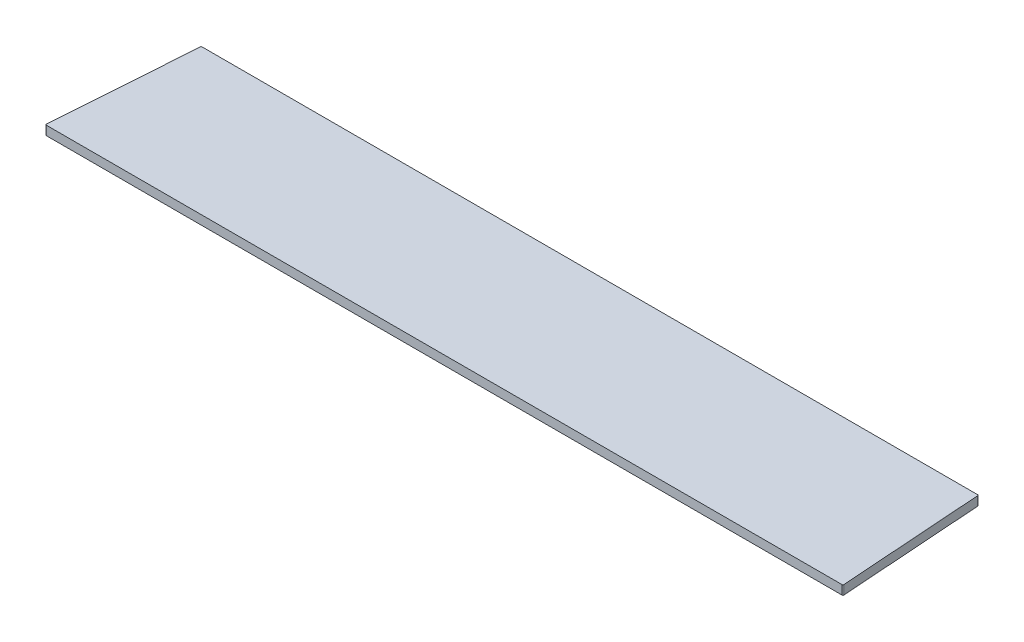
SolidWorks part; units mm, degrees
material "MS-Grade 400"
ref_plane "Front Plane" through (0, 0, 0) normal (0, 0, 1) x (1, 0, 0)
ref_plane "Top Plane" through (0, 0, 0) normal (0, 1, 0) x (1, 0, 0)
ref_plane "Right Plane" through (0, 0, 0) normal (1, 0, 0) x (0, 0, -1)
sketch "Sketch1" plane through (0, 0, 0) normal (0, 1, 0) x (1, 0, 0)
  line L0 (0, 0) -> (0, 160) construction
  line L1 (-426.8117, 160) -> (426.8117, 160)
  line L2 (-426.8117, 160) -> (-438, 0)
  line L3 (-438, 0) -> (438, 0)
  line L4 (426.8117, 160) -> (438, 0)
  dimension "D1" = 876
  dimension "D2" = 160
  dimension "D3" = 86
sheet metal parameters "Sheet-Metal1" thickness 10 parameters "D1"=92
base flange "Base-Flange1" sketch "Sketch1" thickness 10 reverse thickness direction no parameters "D1"=92
fillet "Fillet-1.0" radius 1 4 edges at (438, -5, 0) (426.8117, -5, -160) (-426.8117, -5, -160) (-438, -5, 0)
flat pattern "Flat-Pattern1" [suppressed]
sketch "Bend-Lines1" plane through (0, 0, 0) normal (0, 1, 0) x (1, 0, 0)
sketch3d "Bounding-Box1" [suppressed]
  line L0 (435, 0, 0) -> (-435, 0, 0) construction
  line L1 (435, 160, 0) -> (-435, 160, 0) construction
  line L2 (435, 0, 0) -> (435, 160, 0) construction
  line L3 (-435, 0, 0) -> (-435, 160, 0) construction
